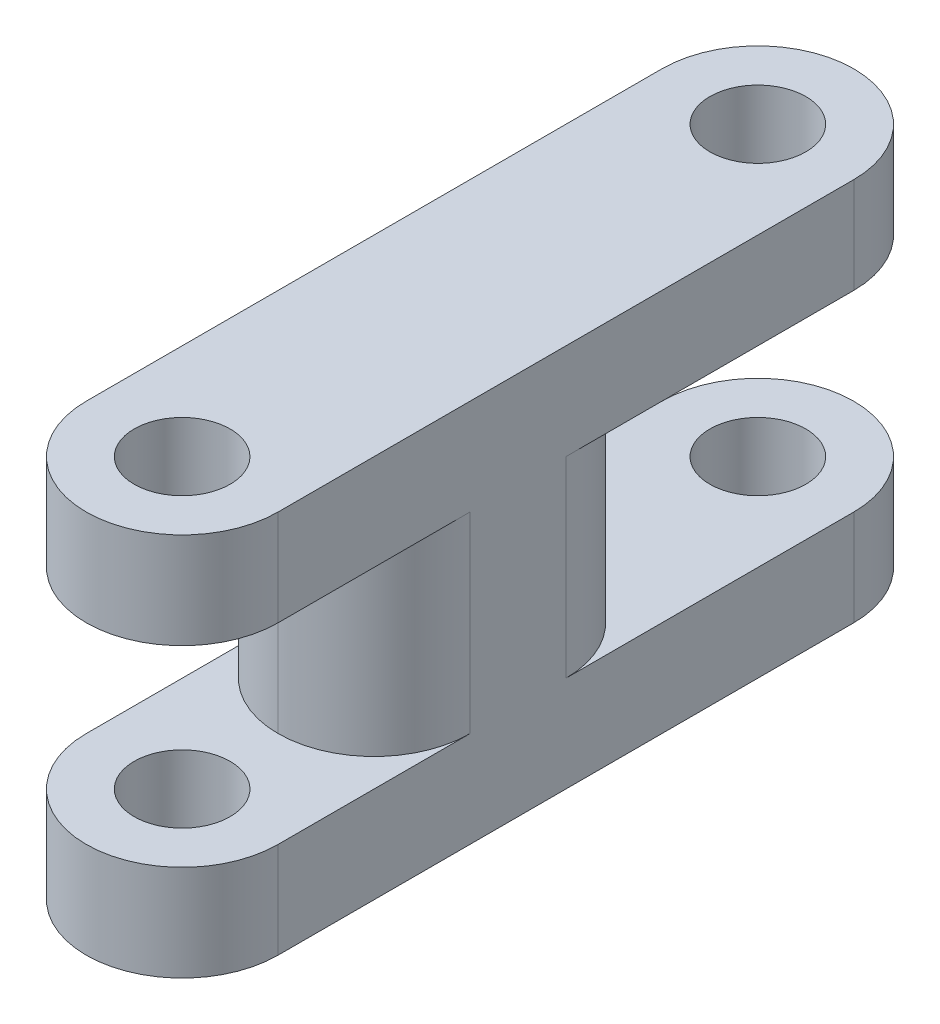
SolidWorks part; units mm, degrees
ref_plane "Front Plane" through (0, 0, 0) normal (0, 0, 1) x (1, 0, 0)
ref_plane "Top Plane" through (0, 0, 0) normal (0, 1, 0) x (1, 0, 0)
ref_plane "Right Plane" through (0, 0, 0) normal (1, 0, 0) x (0, 0, -1)
sketch "Sketch1" plane through (0, 0, 0) normal (0, 1, 0) x (1, 0, 0)
  line L0 (0, 0) -> (0, 30) construction
  line L1 (-5, 0) -> (-5, 30)
  line L2 (5, 0) -> (5, 30)
  arc A0 (-5, 0) -> (5, 0) centre (0, 0) ccw
  arc A1 (5, 30) -> (-5, 30) centre (0, 30) ccw
  circle A2 centre (0, 30) radius 2.5
  circle A3 centre (0, 0) radius 2.5
  point P3 (0, 15)
  dimension "D1" = 5
  dimension "D3" = 5
  dimension "D4" = 5
  dimension "D2" = 30
extrude "Boss-Extrude1" add sketch "Sketch1" along normal blind 20
sketch "Sketch2" plane through (5, 0, 0) normal (1, 0, 0) x (0, 0, -1)
  line L0 (0, 20) -> (30, 20) construction
  line L1 (-5, 15) -> (5, 15)
  line L2 (-5, 15) -> (-5, 5)
  line L3 (-5, 5) -> (5, 5)
  line L4 (5, 15) -> (5, 5)
  line L5 (0, 20) -> (0, 0) construction
  dimension "D1" = 10
  dimension "D2" = 10
  dimension "D3" = 5
  dimension "D4" = 5
extrude "Cut-Extrude1" cut sketch "Sketch2" against normal blind 15
ref_plane "Plane1" through (0, 0, -15) normal (0, 0, 1) x (1, 0, 0)
mirror "Mirror1" about plane through (0, 0, -15) normal (0, 0, 1) of "Cut-Extrude1"
fillet "Fillet1" radius 5 4 edges at (-5, 10, -25) (5, 10, -25) (-5, 10, -5) (5, 10, -5)
sketch "Sketch3" plane through (5, 0, 0) normal (1, 0, 0) x (0, 0, -1)
  line L5 (30, 15) -> (20, 15)
  line L6 (30, 15) -> (30, 5)
  line L7 (30, 5) -> (20, 5)
  line L8 (20, 15) -> (20, 5)
extrude "Cut-Extrude3" cut sketch "Sketch3" against normal blind 10
fillet "Fillet3" radius 5 2 edges at (-5, 10, -20) (5, 10, -20)
